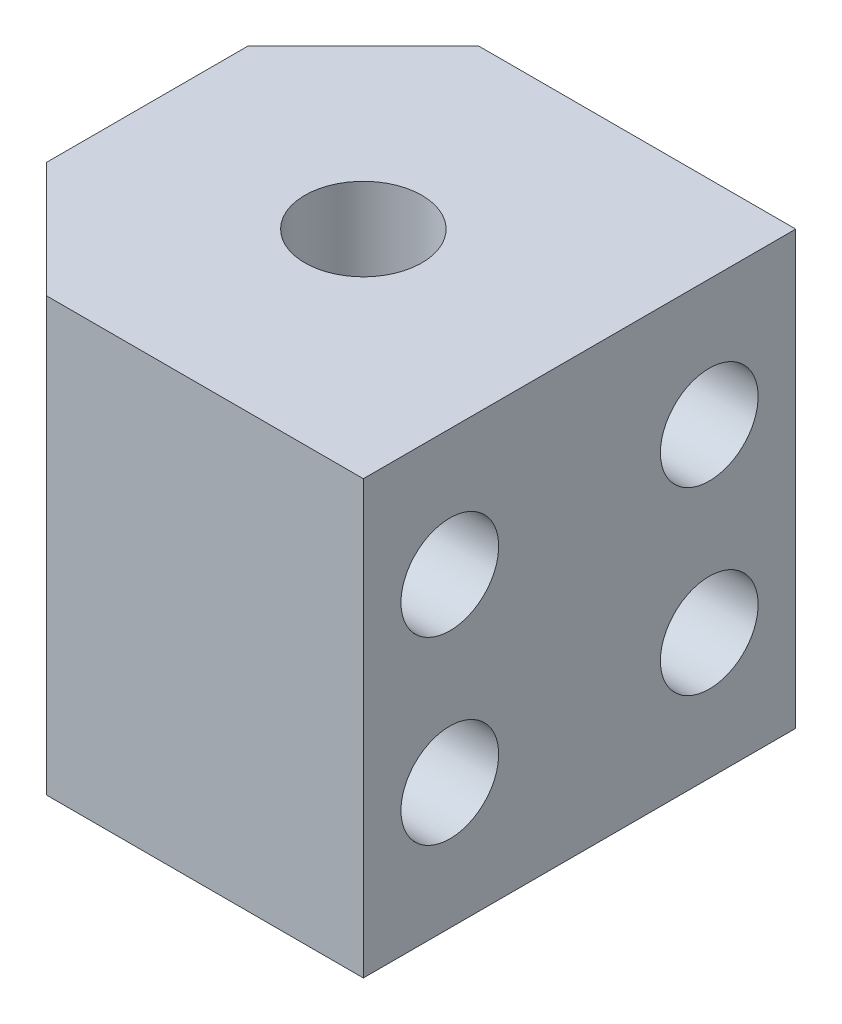
SolidWorks part; units mm, degrees
material "6061-T6 (SS)"
ref_plane "Front Plane" through (0, 0, 0) normal (0, 0, 1) x (1, 0, 0)
ref_plane "Top Plane" through (0, 0, 0) normal (0, 1, 0) x (1, 0, 0)
ref_plane "Right Plane" through (0, 0, 0) normal (1, 0, 0) x (0, 0, -1)
sketch "Sketch1" plane through (0, 0, 0) normal (0, 1, 0) x (1, 0, 0)
  line L0 (-9.525, 9.525) -> (9.525, -9.525) construction
  line L1 (-9.525, 9.525) -> (9.525, 9.525)
  line L2 (-9.525, 9.525) -> (-9.525, -9.525)
  line L3 (-9.525, -9.525) -> (9.525, -9.525)
  line L4 (9.525, 9.525) -> (9.525, -9.525)
  point P4 (0, 0)
  dimension "D1" = 19.05
  dimension "D2" = 19.05
extrude "Boss-Extrude1" add sketch "Sketch1" along normal blind 19.05
hole_wizard "Tapped Hole for #10-24 Helicoil1" positions "Sketch2" profile "Sketch3" tap size "#10-24" standard "Helicoil® Inch" end condition through all
sketch "Sketch2" plane through (0, 0, 0) normal (0, 1, 0) x (1, 0, 0)
  point P0 (0, 0)
sketch "Sketch3" plane through (0, 0, 0) normal (1, 0, 0) x (0, 0, -1)
  line L0 (0, 0) -> (0, 19.05)
  line L1 (0, 19.05) -> (2.5794, 19.05)
  line L2 (2.5794, 19.05) -> (2.5794, 0)
  line L5 (2.5794, 0) -> (0, 0)
  line L11 (0, -6.35) -> (0, 107.95) construction
  dimension "Thru Tap Drill Dia." = 5.1587
  dimension "Thru Tap Drill Depth" = 19.05
cosmetic thread "Hole Thread2" parameters "D1"=18.415, "D2"=6.2865
hole_wizard "CSK for #6 Flat Head Machine Screw1" positions "Sketch4" profile "Sketch5" countersink size "#6" standard "ANSI Inch" end condition through all
sketch "Sketch4" plane through (-9.525, 0, 0) normal (-1, 0, 0) x (0, 0, 1)
  line L1 (5.715, 13.4938) -> (-5.715, 13.4938)
  line L2 (5.715, 13.4938) -> (5.715, 5.5563)
  line L3 (5.715, 5.5563) -> (-5.715, 5.5563)
  line L4 (-5.715, 13.4938) -> (-5.715, 5.5563)
  line L5 (0, 5.5563) -> (0, 0) construction
  line L7 (-9.525, 0) -> (9.525, 0) construction
  line L8 (0, 13.4938) -> (0, 19.05) construction
  line L9 (-9.525, 19.05) -> (9.525, 19.05) construction
  point P0 (5.715, 5.5563)
  point P2 (5.715, 13.4938)
  point P4 (-5.715, 13.4938)
  point P6 (-5.715, 5.5563)
  dimension "D1" = 7.9375
  dimension "D2" = 11.43
sketch "Sketch5" plane through (-9.525, 5.5563, 5.715) normal (0, 1, 0) x (0, 0, 1)
  line L0 (0, 0) -> (0, 19.05)
  line L1 (0, 19.05) -> (2.1526, 19.05)
  line L2 (2.1526, 19.05) -> (2.1526, 6.6798)
  line L3 (2.1526, 6.6798) -> (3.5433, 5.08)
  line L4 (3.5433, 5.08) -> (3.5433, 0)
  line L6 (3.5433, 0) -> (0, 0)
  line L7 (-2.1527, 6.6798) -> (-3.5433, 5.08) construction
  line L11 (0, -6.35) -> (0, 107.95) construction
  dimension "Thru Hole Dia." = 4.3053
  dimension "Thru Hole Depth" = 19.05
  dimension "C'Sink Dia." = 7.0866
  dimension "C'Sink Angle" = 82
  dimension "Head Clearance" = 5.08
sketch "Sketch7" plane through (0, 0, 9.525) normal (0, 0, 1) x (1, 0, 0)
  line L0 (-9.525, 16.51) -> (-4.445, 11.43)
  line L1 (-9.525, 19.05) -> (-9.525, 0) construction
  line L2 (-4.445, 11.43) -> (-4.445, 0)
  line L3 (-4.445, 0) -> (-9.525, 0)
  line L4 (-9.525, 0) -> (-9.525, 16.51)
  line L5 (10.4775, 0) -> (-10.4775, 0) construction
  line L6 (-9.525, 19.05) -> (9.525, 19.05) construction
  dimension "D1" = 2.54
  dimension "D2" = 45
  dimension "D3" = 5.08
extrude "Cut-Extrude2" [suppressed] cut sketch "Sketch7" against normal through all both and the other way through all
chamfer "Chamfer2" distance 5.08 angle 45 2 edges at (-9.525, 9.525, -9.525) (-9.525, 9.525, 9.525)
